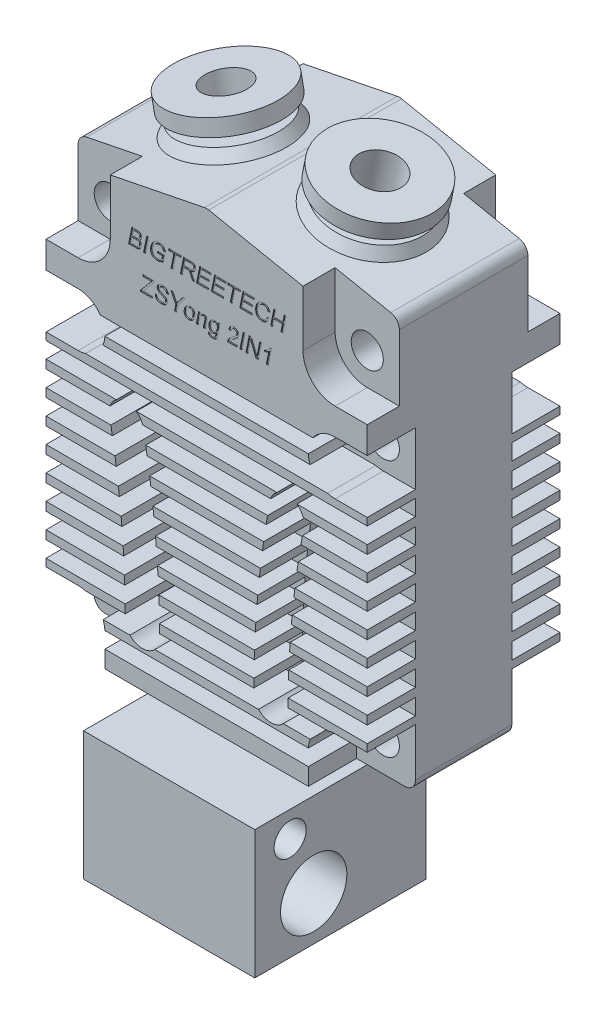
SolidWorks part; units mm, degrees
material "1060 Сплав"
ref_plane "Спереди" through (0, 0, 0) normal (0, 0, 1) x (1, 0, 0)
ref_plane "Сверху" through (0, 0, 0) normal (0, 1, 0) x (1, 0, 0)
ref_plane "Справа" through (0, 0, 0) normal (1, 0, 0) x (0, 0, -1)
sketch "Эскиз1" plane through (0, 0, 0) normal (0, 0, 1) x (1, 0, 0)
  line L0 (-14, 0) -> (14, 0)
  line L1 (15, 1) -> (15, 38.1802)
  line L2 (14.1961, 39.1608) -> (0.1961, 41.9608)
  line L3 (-0.1961, 41.9608) -> (-14.1961, 39.1608)
  line L4 (-15, 38.1802) -> (-15, 1)
  line L5 (0, 0) -> (0, 42) construction
  line L6 (-15, 39) -> (15, 39) construction
  line L7 (-12, 35) -> (12, 35) construction
  line L8 (12, 35) -> (12, 27) construction
  line L9 (12, 27) -> (12, 3) construction
  line L10 (12, 3) -> (-12, 3) construction
  line L11 (-12, 3) -> (-12, 27) construction
  line L12 (-12, 27) -> (-12, 35) construction
  line L13 (-12, 27) -> (12, 27) construction
  arc A0 (-14, 0) -> (-15, 1) centre (-14, 1) cw
  arc A1 (14, 0) -> (15, 1) centre (14, 1) ccw
  arc A2 (-14.1961, 39.1608) -> (-15, 38.1802) centre (-14, 38.1802) ccw
  arc A3 (0.1961, 41.9608) -> (-0.1961, 41.9608) centre (0, 40.9802) ccw
  arc A4 (15, 38.1802) -> (14.1961, 39.1608) centre (14, 38.1802) ccw
  circle A5 centre (12, 3) radius 1.5
  circle A6 centre (-12, 3) radius 1.5
  circle A7 centre (-12, 27) radius 1.5
  circle A8 centre (12, 27) radius 1.5
  circle A9 centre (12, 35) radius 1.5
  circle A10 centre (-12, 35) radius 1.5
  point P27 (0, 3)
  dimension "D1" = 1
  dimension "D9" = 3
  dimension "D2" = 42
  dimension "D3" = 30
  dimension "D4" = 39
  dimension "D5" = 24
  dimension "D6" = 35
  dimension "D7" = 24
  dimension "D8" = 3
extrude "Бобышка-Вытянуть1" add sketch "Эскиз1" along normal blind 18
sketch "Эскиз2" plane through (0, 0, 18) normal (0, 0, 1) x (1, 0, 0)
  line L0 (12, 5.5) -> (15, 5.5)
  line L1 (15, 1) -> (15, 38.1802) construction
  line L2 (9.5, 3) -> (9.5, 0)
  line L3 (-14, 0) -> (14, 0) construction
  line L4 (-9.5, 3) -> (-9.5, 0)
  line L5 (-12, 5.5) -> (-15, 5.5)
  line L6 (-15, 38.1802) -> (-15, 1) construction
  line L7 (-12, 29.5) -> (-15, 29.5)
  line L8 (-15, 29.5) -> (-15, 24.5)
  line L9 (-15, 24.5) -> (-12, 24.5)
  line L10 (12, 24.5) -> (15, 24.5)
  line L11 (15, 24.5) -> (15, 29.5)
  line L12 (15, 29.5) -> (12, 29.5)
  line L13 (12, 32) -> (15, 32)
  line L14 (9, 35) -> (9, 40.2)
  line L15 (14.1961, 39.1608) -> (0.1961, 41.9608) construction
  line L16 (-12, 32) -> (-15, 32)
  line L17 (-9, 35) -> (-9, 40.2)
  line L18 (-15, 5.5) -> (-15, 1)
  line L19 (15, 24.5) -> (15, 38.1802)
  line L20 (9.5, 0) -> (14, 0)
  line L21 (15, 38.1802) -> (15, 32)
  line L22 (-15, 38.1802) -> (-15, 32)
  line L23 (-14, 0) -> (14, 0)
  line L24 (15, 1) -> (15, 38.1802)
  line L25 (14.1961, 39.1608) -> (0.1961, 41.9608)
  line L26 (-0.1961, 41.9608) -> (-14.1961, 39.1608)
  line L27 (-15, 38.1802) -> (-15, 1)
  line L28 (-14, 0) -> (-9.5, 0)
  line L29 (15, 1) -> (15, 5.5)
  line L30 (14.1961, 39.1608) -> (9, 40.2)
  line L31 (-9, 40.2) -> (-14.1961, 39.1608)
  line L32 (-15, 38.1802) -> (-15, 24.5)
  arc A0 (12, 29.5) -> (12, 24.5) centre (12, 27) ccw
  arc A1 (9, 35) -> (12, 32) centre (12, 35) ccw
  arc A2 (-12, 32) -> (-9, 35) centre (-12, 35) ccw
  arc A3 (-12, 24.5) -> (-12, 29.5) centre (-12, 27) ccw
  arc A4 (-9.5, 3) -> (-12, 5.5) centre (-12, 3) ccw
  arc A5 (12, 5.5) -> (9.5, 3) centre (12, 3) ccw
  arc A11 (-15, 1) -> (-14, 0) centre (-14, 1) ccw
  arc A12 (14, 0) -> (15, 1) centre (14, 1) ccw
  arc A13 (15, 38.1802) -> (14.1961, 39.1608) centre (14, 38.1802) ccw
  arc A14 (0.1961, 41.9608) -> (-0.1961, 41.9608) centre (0, 40.9802) ccw
  arc A15 (-14.1961, 39.1608) -> (-15, 38.1802) centre (-14, 38.1802) ccw
  arc A16 (-15, 1) -> (-14, 0) centre (-14, 1) ccw
  arc A17 (14, 0) -> (15, 1) centre (14, 1) ccw
  arc A18 (15, 38.1802) -> (14.1961, 39.1608) centre (14, 38.1802) ccw
  arc A20 (-14.1961, 39.1608) -> (-15, 38.1802) centre (-14, 38.1802) ccw
  arc M11 (-15, 1) -> (-14, 0) centre (-14, 1) ccw
  line M12 (-14, 0) -> (14, 0)
  arc M13 (14, 0) -> (15, 1) centre (14, 1) ccw
  line M14 (15, 1) -> (15, 38.1802)
  arc M15 (15, 38.1802) -> (14.1961, 39.1608) centre (14, 38.1802) ccw
  line M16 (14.1961, 39.1608) -> (0.1961, 41.9608)
  line M18 (-0.1961, 41.9608) -> (-14.1961, 39.1608)
  arc M19 (-14.1961, 39.1608) -> (-15, 38.1802) centre (-14, 38.1802) ccw
  line M20 (-15, 38.1802) -> (-15, 1)
  circle M21 centre (-12, 3) radius 1.5
  circle M22 centre (-12, 27) radius 1.5
  circle M23 centre (12, 27) radius 1.5
  circle M24 centre (12, 3) radius 1.5
  circle M25 centre (12, 35) radius 1.5
  circle M26 centre (-12, 35) radius 1.5
  dimension "D1" = 5
  dimension "D2" = 6
  dimension "D3" = 0
extrude "Вырез-Вытянуть1" cut sketch "Эскиз2" against normal blind 3 contours L16 A2 L17 M18 M19 M20 M26 | L14 A1 L13 M14 M15 M16 M25 | L12 A0 L10 M14 M23 | L9 A3 L7 M20 M22 | L0 A5 L2 M12 M13 M14 M24 | L4 A4 L5 M20 M11 M12 M21 region at (13.5, 5.4222, 18) region at (13.5, 24.5743, 18) region at (-11.75, 0.0778, 18) region at (13.5, 32.1016, 18) region at (-14.9257, 27, 18) region at (-14.8984, 35.0901, 18)
sketch "Эскиз3" plane through (0, 0, 15) normal (0, 0, 1) x (1, 0, 0)
  line L3 (15, 29.5) -> (12, 29.5)
  line L4 (12, 24.5) -> (15, 24.5)
  line L5 (15, 24.5) -> (15, 29.5)
  line L6 (15, 29.5) -> (12, 29.5)
  line L7 (12, 24.5) -> (15, 24.5)
  line L8 (15, 24.5) -> (15, 29.5)
  line L9 (-15, 24.5) -> (-12, 24.5)
  line L10 (-12, 29.5) -> (-15, 29.5)
  line L11 (-15, 29.5) -> (-15, 24.5)
  line L12 (-15, 24.5) -> (-12, 24.5)
  line L13 (-12, 29.5) -> (-15, 29.5)
  line L14 (-15, 29.5) -> (-15, 24.5)
  line L16 (-9.5, 0) -> (-9.5, 3)
  line L17 (-12, 5.5) -> (-15, 5.5)
  line L18 (-15, 5.5) -> (-15, 1)
  line L19 (-14, 0) -> (-9.5, 0)
  line L20 (-9.5, 0) -> (-9.5, 3)
  line L21 (-12, 5.5) -> (-15, 5.5)
  line L22 (-15, 5.5) -> (-15, 1)
  line L23 (-14, 0) -> (-9.5, 0)
  line L24 (15, 5.5) -> (12, 5.5)
  line L25 (9.5, 3) -> (9.5, 0)
  line L26 (9.5, 0) -> (14, 0)
  line L27 (15, 1) -> (15, 5.5)
  line L28 (15, 5.5) -> (12, 5.5)
  line L29 (9.5, 3) -> (9.5, 0)
  line L30 (9.5, 0) -> (14, 0)
  line L31 (15, 1) -> (15, 5.5)
  arc A1 (12, 29.5) -> (12, 24.5) centre (12, 27) ccw
  arc A2 (12, 29.5) -> (12, 24.5) centre (12, 27) ccw
  arc A3 (-12, 24.5) -> (-12, 29.5) centre (-12, 27) ccw
  arc A4 (-12, 24.5) -> (-12, 29.5) centre (-12, 27) ccw
  arc A6 (-9.5, 3) -> (-12, 5.5) centre (-12, 3) ccw
  arc A7 (-15, 1) -> (-14, 0) centre (-14, 1) ccw
  arc A8 (-9.5, 3) -> (-12, 5.5) centre (-12, 3) ccw
  arc A9 (-15, 1) -> (-14, 0) centre (-14, 1) ccw
  arc A10 (12, 5.5) -> (9.5, 3) centre (12, 3) ccw
  arc A11 (14, 0) -> (15, 1) centre (14, 1) ccw
  arc A12 (12, 5.5) -> (9.5, 3) centre (12, 3) ccw
  arc A13 (14, 0) -> (15, 1) centre (14, 1) ccw
  dimension "D1" = 0
  dimension "D2" = 0
  dimension "D3" = 0
  dimension "D4" = 0
extrude "Вырез-Вытянуть2" cut sketch "Эскиз3" against normal blind 1.5
sketch "Эскиз4" plane through (0, 0, 18) normal (0, 0, 1) x (1, 0, 0)
  line L5 (15, 1) -> (15, 5.5) construction
  line L6 (15, 1.6) -> (-15, 1.6)
  line L7 (15, 1.6) -> (15, 3.1)
  line L8 (15, 3.1) -> (-15, 3.1)
  line L9 (-15, 1.6) -> (-15, 3.1)
  line L10 (-15, 5.5) -> (-15, 1) construction
  line L11 (-9.5, 0) -> (9.5, 0) construction
  line L12 (15, 5.4) -> (-15, 5.4)
  line L13 (-15, 3.9) -> (-15, 5.4)
  line L14 (15, 3.9) -> (-15, 3.9)
  line L15 (15, 3.9) -> (15, 5.4)
  line L16 (15, 7.7) -> (-15, 7.7)
  line L17 (-15, 6.2) -> (-15, 7.7)
  line L18 (15, 6.2) -> (-15, 6.2)
  line L19 (15, 6.2) -> (15, 7.7)
  line L20 (15, 10) -> (-15, 10)
  line L21 (-15, 8.5) -> (-15, 10)
  line L22 (15, 8.5) -> (-15, 8.5)
  line L23 (15, 8.5) -> (15, 10)
  line L24 (15, 12.3) -> (-15, 12.3)
  line L25 (-15, 10.8) -> (-15, 12.3)
  line L26 (15, 10.8) -> (-15, 10.8)
  line L27 (15, 10.8) -> (15, 12.3)
  line L28 (15, 14.6) -> (-15, 14.6)
  line L29 (-15, 13.1) -> (-15, 14.6)
  line L30 (15, 13.1) -> (-15, 13.1)
  line L31 (15, 13.1) -> (15, 14.6)
  line L32 (15, 16.9) -> (-15, 16.9)
  line L33 (-15, 15.4) -> (-15, 16.9)
  line L34 (15, 15.4) -> (-15, 15.4)
  line L35 (15, 15.4) -> (15, 16.9)
  line L36 (15, 19.2) -> (-15, 19.2)
  line L37 (-15, 17.7) -> (-15, 19.2)
  line L38 (15, 17.7) -> (-15, 17.7)
  line L39 (15, 17.7) -> (15, 19.2)
  line L40 (15, 21.5) -> (-15, 21.5)
  line L41 (-15, 20) -> (-15, 21.5)
  line L42 (15, 20) -> (-15, 20)
  line L43 (15, 20) -> (15, 21.5)
  line L44 (15, 23.8) -> (-15, 23.8)
  line L45 (-15, 22.3) -> (-15, 23.8)
  line L46 (15, 22.3) -> (-15, 22.3)
  line L47 (15, 22.3) -> (15, 23.8)
  line L48 (15, 26.1) -> (-15, 26.1)
  line L49 (-15, 24.6) -> (-15, 26.1)
  line L50 (15, 24.6) -> (-15, 24.6)
  line L51 (15, 24.6) -> (15, 26.1)
  line L52 (15, 28.4) -> (-15, 28.4)
  line L53 (-15, 26.9) -> (-15, 28.4)
  line L54 (15, 26.9) -> (-15, 26.9)
  line L55 (15, 26.9) -> (15, 28.4)
  dimension "D1" = 1.6
  dimension "D2" = 12
  dimension "D3" = 1.5
extrude "Вырез-Вытянуть3" cut sketch "Эскиз4" against normal up to surface (4.5 mm away) up to face at (-10.5, 27, 13.5)
ref_plane "Плоскость1" through (0, 0, 9) normal (0, 0, 1) x (1, 0, 0)
mirror "Зеркальное отражение1" about plane through (0, 0, 9) normal (0, 0, 1) of "Вырез-Вытянуть3", "Вырез-Вытянуть2", "Вырез-Вытянуть1"
sketch "Эскиз5" plane through (0, 0, 18) normal (0, 0, 1) x (1, 0, 0)
  line L0 (0, 0) -> (0, 41.9802) construction
  line L1 (-6, 5) -> (6, 5) construction
  line L2 (-7.5, 21) -> (7.5, 21) construction
  line L3 (-9.5, 0) -> (9.5, 0) construction
  line L6 (-4.4, 5) -> (-4.4, 10.2554) construction
  line L7 (-7.6, 5) -> (-7.6, 6.0377) construction
  arc A0 (0.1961, 41.9608) -> (-0.1961, 41.9608) centre (0, 40.9802) ccw construction
  arc A2 (-5.9, 21) -> (-9.0721, 20.7026) centre (-7.5, 21) ccw
  arc A3 (-7.6, 5) -> (-4.4, 5) centre (-6, 5) ccw
  arc A5 (-4.4, 5) -> (-5.9279, 21.2974) centre (-92.0833, 5) ccw
  arc A6 (-9.0721, 20.7026) -> (-7.6, 5) centre (-92.0833, 5) cw
  arc A7 (4.4, 5) -> (5.9279, 21.2974) centre (92.0833, 5) cw
  arc A8 (7.6, 5) -> (4.4, 5) centre (6, 5) cw
  arc A9 (9.0721, 20.7026) -> (7.6, 5) centre (92.0833, 5) ccw
  arc A10 (5.9, 21) -> (9.0721, 20.7026) centre (7.5, 21) cw
  point P10 (0, 21)
  point P11 (0, 5)
  dimension "D5" = 1.6
  dimension "D1" = 5
  dimension "D2" = 12
  dimension "D3" = 15
  dimension "D4" = 16
extrude "Вырез-Вытянуть4" cut sketch "Эскиз5" against normal up to surface (18 mm away) contours A2 A6 A3 A5 | A10 A7 A8 A9 region at (-6.5343, 13.0202, 18) region at (6.5343, 13.0202, 18) up to face at (0, 33.5259, 0)
sketch "Эскиз6" plane through (0, 0, 0) normal (0, -1, 0) x (1, 0, 0)
  line L0 (0, 0) -> (0, 18) construction
  line L1 (-9.5, 18) -> (9.5, 18) construction
  circle A0 centre (0, 9) radius 2.5
  dimension "D1" = 5
extrude "Вырез-Вытянуть5" cut sketch "Эскиз6" against normal blind 25
sketch "Эскиз7" plane through (0, 0, 9) normal (0, 0, 1) x (1, 0, 0)
  line L0 (6.501, 40.6998) -> (4.3457, 29.9233) construction
  line L1 (9, 40.2) -> (0.1961, 41.9608) construction
  line L6 (8.4621, 40.3076) -> (11.5019, 39.6996)
  line L7 (11.5019, 39.6996) -> (11.1097, 40.7979)
  line L8 (11.1097, 40.7979) -> (9.6388, 41.092)
  line L9 (9.6388, 41.092) -> (9.8349, 42.0726)
  line L10 (9.8349, 42.0726) -> (11.7961, 41.6804)
  line L11 (11.7961, 41.6804) -> (12.0903, 43.1513)
  line L12 (12.0903, 43.1513) -> (9.1485, 43.7396)
  line L13 (9.1485, 43.7396) -> (8.4621, 40.3076)
  line L14 (6.501, 40.6998) -> (8.4621, 40.3076) construction
  line L15 (0, 41.9802) -> (0, 38.4176) construction
  line L16 (6.501, 40.6998) -> (1.5, 41.7) construction
  line L17 (11.5019, 39.6996) -> (6.501, 40.6998) construction
  arc A0 (0.1961, 41.9608) -> (-0.1961, 41.9608) centre (0, 40.9802) ccw construction
  dimension "D1" = 4
  dimension "D2" = 10.2
  dimension "D3" = 9
  dimension "D4" = 10
  dimension "D5" = 6
  dimension "D6" = 1
  dimension "D7" = 1
  dimension "D8" = 1.5
  dimension "D9" = 1.5
revolve "Повернуть1" add sketch "Эскиз7" angle 360 about L0
mirror "Зеркальное отражение2" about plane through (0, 0, 0) normal (1, 0, 0) of "Повернуть1"
sketch "Эскиз8" plane through (-8.0769, 40.3846, 0) normal (-0.1961, 0.9806, 0) x (0.9806, 0.1961, 0)
  circle A1 centre (1.6072, -9) radius 2
  circle A2 centre (1.6072, -9) radius 2
  dimension "D1" = 0
extrude "Вырез-Вытянуть6" cut sketch "Эскиз8" against normal blind 30
sketch "Эскиз9" plane through (8.0769, 40.3846, 0) normal (0.1961, 0.9806, 0) x (0.9806, -0.1961, 0)
  circle A1 centre (-1.6072, -9) radius 2
  circle A2 centre (-1.6072, -9) radius 2
  dimension "D1" = 0
extrude "Вырез-Вытянуть7" cut sketch "Эскиз9" against normal blind 30
sketch "Эскиз10" plane through (0, 0, 0) normal (0, -1, 0) x (1, 0, 0)
  circle A0 centre (0, 9) radius 1
  circle A1 centre (0, 9) radius 2.5 construction
  circle A2 centre (0, 9) radius 2.5
  dimension "D1" = 2
extrude "Бобышка-Вытянуть2" add sketch "Эскиз10" along normal blind 10 and the other way blind 20
sketch "Эскиз11" plane through (0, 0, 0) normal (0, -1, 0) x (1, 0, 0)
  line L0 (0, 5.5) -> (0, 21.5) construction
  line L1 (-8, 21.5) -> (8, 21.5)
  line L2 (-8, 21.5) -> (-8, 5.5)
  line L3 (-8, 5.5) -> (8, 5.5)
  line L4 (8, 21.5) -> (8, 5.5)
  line L5 (-1, 9) -> (1, 9) construction
  circle A0 centre (0, 9) radius 1 construction
  circle A1 centre (0, 9) radius 2.5 construction
  circle A2 centre (0, 9) radius 2.5
  point P11 (0, 9)
  dimension "D1" = 16
  dimension "D2" = 16
  dimension "D3" = 3.5
extrude "Бобышка-Вытянуть3" add sketch "Эскиз11" along normal blind 12 from offset 2.5
sketch "Эскиз12" plane through (8, 0, 0) normal (1, 0, 0) x (0, 0, -1)
  line L0 (-21.5, -14.5) -> (-21.5, -2.5) construction
  line L1 (-5.5, -2.5) -> (-21.5, -2.5) construction
  line L2 (-5.5, -14.5) -> (-21.5, -14.5) construction
  circle A0 centre (-16, -10.4) radius 3.1
  circle A1 centre (-18.2, -4.9) radius 1.5
  dimension "D1" = 6.2
  dimension "D2" = 3
  dimension "D3" = 3.3
  dimension "D4" = 2.4
  dimension "D5" = 5.5
  dimension "D6" = 4.1
extrude "Вырез-Вытянуть8" cut sketch "Эскиз12" against normal up to surface (16 mm away) up to face at (-8, -8.5, 13.5)
sketch "Эскиз13" plane through (0, 0, 18) normal (0, 0, 1) x (1, 0, 0)
  line L0 (-7.9523, 35.4961) -> (7.9523, 35.4961) construction
  line L1 (0, 0) -> (0, 35.4961) construction
  text T0 "BIGTREETECH\r\nZSYong 2IN1" font "Arial" height 1.5
extrude "Вырез-Вытянуть9" cut sketch "Эскиз13" against normal blind 0.1
